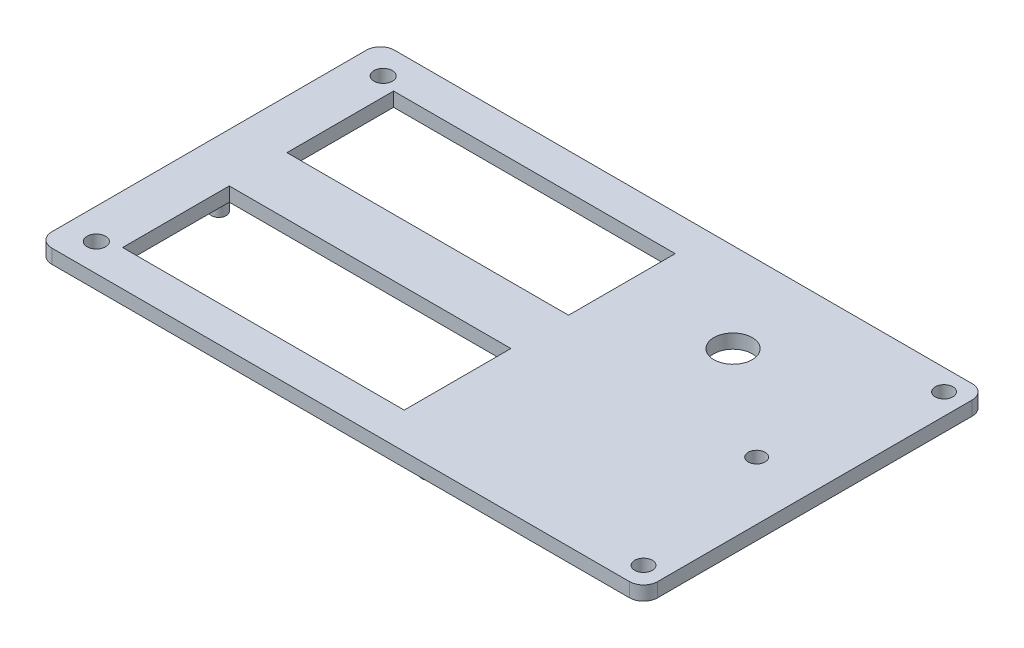
SolidWorks part; units mm, degrees
ref_plane "Front Plane" through (0, 0, 0) normal (0, 0, 1) x (1, 0, 0)
ref_plane "Top Plane" through (0, 0, 0) normal (0, 1, 0) x (1, 0, 0)
ref_plane "Right Plane" through (0, 0, 0) normal (1, 0, 0) x (0, 0, -1)
sketch "Sketch1" plane through (0, 0, 0) normal (0, 1, 0) x (1, 0, 0)
  line L0 (0, 14.8209) -> (0, -14.8209) construction
  line L1 (-33.02, 28.3718) -> (33.02, 28.3718) construction
  line L2 (-33.02, 28.3718) -> (-33.02, 1.27) construction
  line L3 (-33.02, 1.27) -> (33.02, 1.27) construction
  line L4 (33.02, 28.3718) -> (33.02, 1.27) construction
  line L5 (-33.02, 28.3718) -> (33.02, 1.27) construction
  line L6 (-33.02, 1.27) -> (33.02, 28.3718) construction
  line L7 (-33.02, -28.3718) -> (33.02, -28.3718) construction
  line L8 (-33.02, -28.3718) -> (-33.02, -1.27) construction
  line L9 (-33.02, -1.27) -> (33.02, -1.27) construction
  line L10 (33.02, -28.3718) -> (33.02, -1.27) construction
  line L11 (-33.02, -28.3718) -> (33.02, -1.27) construction
  line L12 (-33.02, -1.27) -> (33.02, -28.3718) construction
  line L18 (-35.56, -30.9118) -> (73.7235, -30.9118)
  line L19 (73.7235, -30.9118) -> (73.7235, 30.9118)
  line L20 (73.7235, 30.9118) -> (-35.56, 30.9118)
  line L21 (33.02, 14.8209) -> (44.1325, 14.8209) construction
  line L22 (-33.02, 14.8209) -> (33.02, 14.8209) construction
  line L23 (55.245, 16.0655) -> (71.1835, 16.0655) construction
  line L24 (55.245, 16.0655) -> (55.245, -16.0655) construction
  line L25 (55.245, -16.0655) -> (71.1835, -16.0655) construction
  line L26 (71.1835, 16.0655) -> (71.1835, -16.0655) construction
  line L31 (24.08, 5.2007) -> (-26.72, 5.2007)
  line L32 (24.08, 5.2007) -> (24.08, 24.4411)
  line L33 (24.08, 24.4411) -> (-26.72, 24.4412)
  line L34 (-26.72, 5.2007) -> (-26.72, 24.4412)
  line L35 (24.08, 5.2007) -> (-26.72, 24.4412) construction
  line L36 (24.08, 24.4411) -> (-26.72, 5.2007) construction
  line L37 (24.08, -24.4411) -> (-26.72, -24.4411)
  line L38 (24.08, -24.4411) -> (24.08, -5.2007)
  line L39 (24.08, -5.2007) -> (-26.72, -5.2007)
  line L40 (-26.72, -24.4411) -> (-26.72, -5.2007)
  line L41 (24.08, -24.4411) -> (-26.72, -5.2007) construction
  line L42 (24.08, -5.2007) -> (-26.72, -24.4411) construction
  line L43 (-55, 0) -> (55, 0) construction
  line L45 (63.2143, 16.0655) -> (63.2143, -16.0655) construction
  line L46 (-35.56, 30.9118) -> (-35.56, -30.9118)
  line L47 (-77.9653, 29.2861) -> (-77.9653, 54.4861) construction
  line L48 (-78.9653, 55.4861) -> (-142.9653, 55.4861) construction
  line L49 (-143.9653, 54.4861) -> (-143.9653, 29.2861) construction
  line L50 (-142.9653, 28.2861) -> (-78.9653, 28.2861) construction
  line L51 (-33.02, -14.8209) -> (33.02, -14.8209) construction
  circle A0 centre (44.1325, 14.8209) radius 8.5725 construction
  circle A1 centre (44.1325, 14.8209) radius 3.4607
  circle A2 centre (-30.02, 25.8718) radius 1.6637
  circle A3 centre (30.02, 25.8718) radius 1.6637
  circle A4 centre (-30.02, 3.77) radius 1.6637
  circle A5 centre (30.02, 3.77) radius 1.6637
  circle A6 centre (30.02, -3.77) radius 1.6637
  circle A7 centre (-30.02, -3.77) radius 1.6637
  circle A8 centre (-30.02, -25.8718) radius 1.6637
  circle A9 centre (30.02, -25.8718) radius 1.6637
  circle A10 centre (63.2143, 0) radius 1.524
  circle A12 centre (69.9135, 27.1018) radius 1.5875
  circle A13 centre (69.9135, -27.1018) radius 1.5875
  arc A14 (-77.9653, 54.4861) -> (-78.9653, 55.4861) centre (-78.9653, 54.4861) ccw construction
  arc A15 (-142.9653, 55.4861) -> (-143.9653, 54.4861) centre (-142.9653, 54.4861) ccw construction
  arc A16 (-143.9653, 29.2861) -> (-142.9653, 28.2861) centre (-142.9653, 29.2861) ccw construction
  arc A17 (-78.9653, 28.2861) -> (-77.9653, 29.2861) centre (-78.9653, 29.2861) ccw construction
  arc A18 (-139.5173, 53.4271) -> (-142.4133, 51.845) centre (-140.9653, 52.6361) ccw construction
  arc A19 (-142.4133, 51.845) -> (-139.5173, 53.4271) centre (-140.9653, 52.6361) ccw construction
  arc A20 (-139.5173, 31.9271) -> (-142.4133, 30.345) centre (-140.9653, 31.1361) ccw construction
  arc A21 (-142.4133, 30.345) -> (-139.5173, 31.9271) centre (-140.9653, 31.1361) ccw construction
  arc A22 (-82.4133, 30.345) -> (-79.5173, 31.9271) centre (-80.9653, 31.1361) ccw construction
  arc A23 (-79.5173, 31.9271) -> (-82.4133, 30.345) centre (-80.9653, 31.1361) ccw construction
  arc A24 (-79.5173, 53.4271) -> (-82.4133, 51.845) centre (-80.9653, 52.6361) ccw construction
  arc A25 (-82.4133, 51.845) -> (-79.5173, 53.4271) centre (-80.9653, 52.6361) ccw construction
  point P0 (0, 14.8209)
  point P5 (0, -14.8209)
  point P10 (0, 0)
  point P13 (0, 0)
  point P31 (55.245, 0)
  point P88 (-26.72, 14.8209)
  point P90 (-26.72, -14.8209)
  dimension "D6" = 2.54
  dimension "D7" = 17.145
  dimension "D8" = 6.9215
  dimension "D16" = 3.3274
  dimension "D17" = 3
  dimension "D18" = 3
  dimension "D19" = 3.048
  dimension "D20" = 3.175
  dimension "D23" = 3.81
  dimension "D25" = 109.2835
  dimension "D26" = 61.8236
  dimension "D31" = 2.5
  dimension "D1" = 66.04
  dimension "D2" = 27.1018
  dimension "D3" = 2.54
  dimension "D4" = 2.54
  dimension "D5" = 2.54
  dimension "D9" = 2.54
  dimension "D10" = 2.54
  dimension "D11" = 2.54
  dimension "D12" = 32.131
  dimension "D13" = 15.9385
  dimension "D14" = 19.2405
  dimension "D15" = 50.8
  dimension "D21" = 3.81
  dimension "D22" = 3.81
  dimension "D24" = 3.81
  dimension "D27" = 5.54
  dimension "D28" = 5.04
  dimension "D29" = 5.04
  dimension "D30" = 5.54
  dimension "D32" = 60
  dimension "D33" = 66
  dimension "D34" = 27.2
  dimension "D35" = 21.5
  dimension "D36" = 2.85
  dimension "D37" = 3
  dimension "D38" = 6.3
extrude "Boss-Extrude1" add sketch "Sketch1" along normal blind 2.54
sketch "Sketch5" plane through (0, 0, 0) normal (0, -1, 0) x (1, 0, 0)
  line L0 (24.08, -5.2007) -> (24.08, -24.4411) construction
  line L1 (25.985, -9.5822) -> (28.525, -9.5822)
  line L2 (25.985, -9.5822) -> (25.985, -20.0597)
  line L3 (25.985, -20.0597) -> (28.525, -20.0597)
  line L4 (28.525, -9.5822) -> (28.525, -20.0597)
  line L5 (24.08, -14.8209) -> (11.0317, -14.8209) construction
  line L6 (55, 0) -> (-55, 0) construction
  line L7 (25.985, 20.0597) -> (28.525, 20.0597)
  line L8 (28.525, 9.5822) -> (28.525, 20.0597)
  line L9 (25.985, 9.5822) -> (28.525, 9.5822)
  line L10 (25.985, 9.5822) -> (25.985, 20.0597)
  line L11 (44.1325, -14.8209) -> (35.56, -14.8209) construction
  line L13 (34.925, -16.0909) -> (36.195, -16.0909) construction
  line L14 (34.925, -16.0909) -> (34.925, -13.5509) construction
  line L15 (34.925, -13.5509) -> (36.195, -13.5509) construction
  line L16 (36.195, -16.0909) -> (36.195, -13.5509) construction
  line L17 (34.925, -16.0909) -> (36.195, -13.5509) construction
  line L18 (34.925, -13.5509) -> (36.195, -16.0909) construction
  line L25 (71.1835, 12.6365) -> (55.245, 12.6365)
  line L26 (55.245, 16.0655) -> (55.245, 12.6365)
  line L27 (71.1835, 16.0655) -> (55.245, 16.0655)
  line L28 (71.1835, 16.0655) -> (71.1835, 12.6365)
  point P8 (25.985, -14.8209)
  dimension "D1" = 1.905
  dimension "D2" = 10.4775
  dimension "D3" = 2.54
  dimension "D4" = 8.5725
  dimension "D5" = 1.27
  dimension "D6" = 2.54
extrude "Cut-Extrude1" cut sketch "Sketch5" against normal blind 1.905
fillet "Fillet1" radius 1.27 16 edges at (27.255, 1.905, 20.0597) (28.525, 1.905, 14.8209) (27.255, 1.905, 9.5822) (25.985, 1.905, 14.8209) (27.255, 1.905, -9.5822) (28.525, 1.905, -14.8209) (27.255, 1.905, -20.0597) (25.985, 1.905, -14.8209) (71.1835, 0.9525, 12.6365) (71.1835, 1.905, 14.351) (71.1835, 0.9525, 16.0655) (63.2143, 1.905, 16.0655) (63.2143, 1.905, 12.6365) (55.245, 1.905, 14.351) (55.245, 0.9525, 12.6365) (55.245, 0.9525, 16.0655)
fillet "Fillet2" radius 2.54 4 edges at (73.7235, 1.27, 30.9118) (73.7235, 1.27, -30.9118) (-35.56, 1.27, 30.9118) (-35.56, 1.27, -30.9118)
sketch "Sketch6" plane through (0, 0, 0) normal (0, -1, 0) x (1, 0, 0)
  circle A0 centre (-30.02, 3.77) radius 1.6637
  circle A1 centre (-30.02, -3.77) radius 1.6637
  circle A2 centre (30.02, -25.8718) radius 1.6637
  circle A3 centre (30.02, 25.8718) radius 1.6637
  circle A4 centre (30.02, 3.77) radius 1.6637
  circle A5 centre (30.02, -3.77) radius 1.6637
extrude "Boss-Extrude2" add sketch "Sketch6" against normal up to surface (2.54 mm away) up to face at (69.9135, 2.54, -25.5143)
sketch "Sketch7" plane through (0, 0, 0) normal (0, -1, 0) x (1, 0, 0)
  circle A0 centre (-30.02, 3.77) radius 1.3335
  circle A1 centre (-30.02, -3.77) radius 1.3335
  circle A2 centre (30.02, -25.8718) radius 1.3335
  circle A3 centre (30.02, 25.8718) radius 1.3335
  circle A4 centre (30.02, -3.77) radius 1.3335
  circle A5 centre (30.02, 3.77) radius 1.3335
  dimension "D1" = 2.667
extrude "Boss-Extrude3" add sketch "Sketch7" along normal blind 3.81
